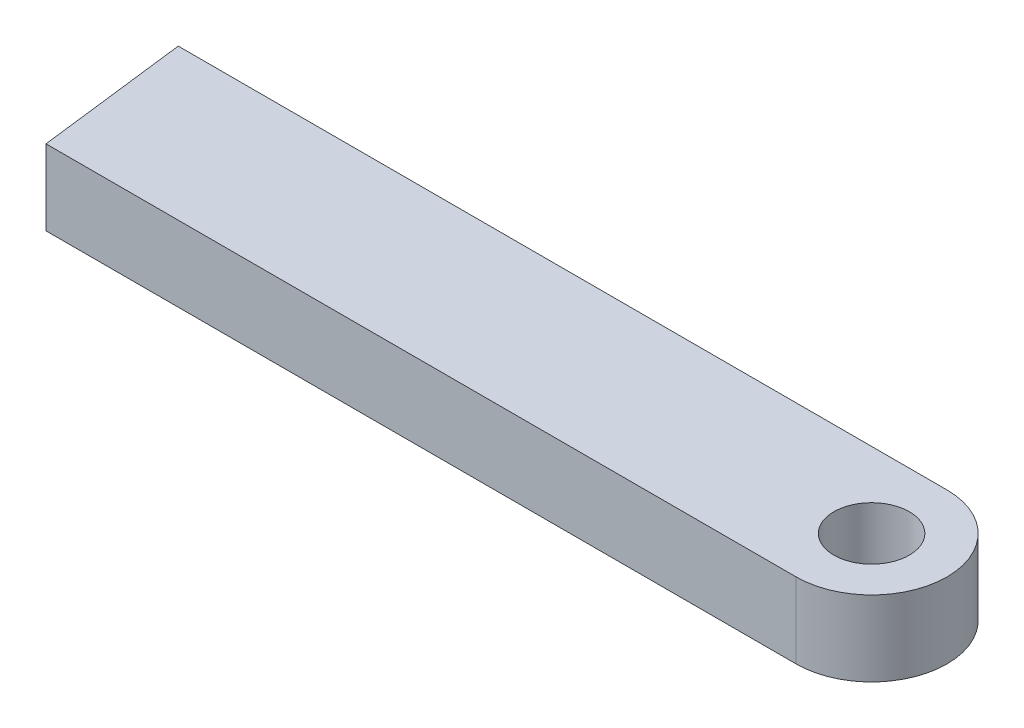
SolidWorks part; units mm, degrees
ref_plane "Plan de face" through (0, 0, 0) normal (0, 0, 1) x (1, 0, 0)
ref_plane "Plan de dessus" through (0, 0, 0) normal (0, 1, 0) x (1, 0, 0)
ref_plane "Plan de droite" through (0, 0, 0) normal (1, 0, 0) x (0, 0, -1)
sketch "Esquisse1" plane through (0, 0, 0) normal (0, 1, 0) x (1, 0, 0)
  line L0 (-49.7616, -5) -> (0, -5)
  line L1 (0, 5) -> (-50.9894, 5)
  line L2 (-50.9894, 5) -> (-49.7616, -5)
  arc A0 (0, -5) -> (0, 5) centre (0, 0) ccw
  circle A1 centre (0, 0) radius 2.5
  dimension "D3" = 5
  dimension "D1" = 10
  dimension "D2" = 50
  dimension "D4" = 83
extrude "Boss.-Extru.1" add sketch "Esquisse1" along normal mid plane 5
hole_wizard "Trou taraudé M3x0.51" positions "Esquisse3" profile "Esquisse2" tap size "M3x0.5" standard "Ansi Metric"
sketch "Esquisse3" plane through (-49.6273, 0, 6.0935) normal (-0.9925, 0, 0.1219) x (0.1219, 0, 0.9925)
  line L0 (-11.1768, -2.5) -> (-1.1017, -2.5) construction
  line L1 (-6.1392, -2.5) -> (-6.1392, -0.25) construction
  point P7 (-6.1392, -0.25)
  dimension "D1" = 2.25
sketch "Esquisse2" plane through (-50.3755, -0.25, 0) normal (0, 1, 0) x (0.1219, 0, 0.9925)
  line L0 (0, 0) -> (0, 13.2511)
  line L1 (0, 13.2511) -> (1.25, 12.5)
  line L2 (1.25, 12.5) -> (1.25, 0.275)
  line L3 (1.25, 0.275) -> (1.525, 0)
  line L5 (1.525, 0) -> (0, 0)
  line L6 (-1.25, 0.275) -> (-1.525, 0) construction
  line L10 (0, 13.2511) -> (-1.25, 12.5) construction
  line L11 (0, -6.35) -> (0, 107.95) construction
  dimension "Diamètre du trou pour taraudage" = 2.5
  dimension "Profondeur du trou pour taraudage" = 12.5
  dimension "Diamètre du fraisage entrant" = 3.05
  dimension "Angle du fraisage entrant" = 90
  dimension "Angle de pointe" = 118
cosmetic thread "Filetage de perçage1" parameters "D1"=10, "D2"=3
